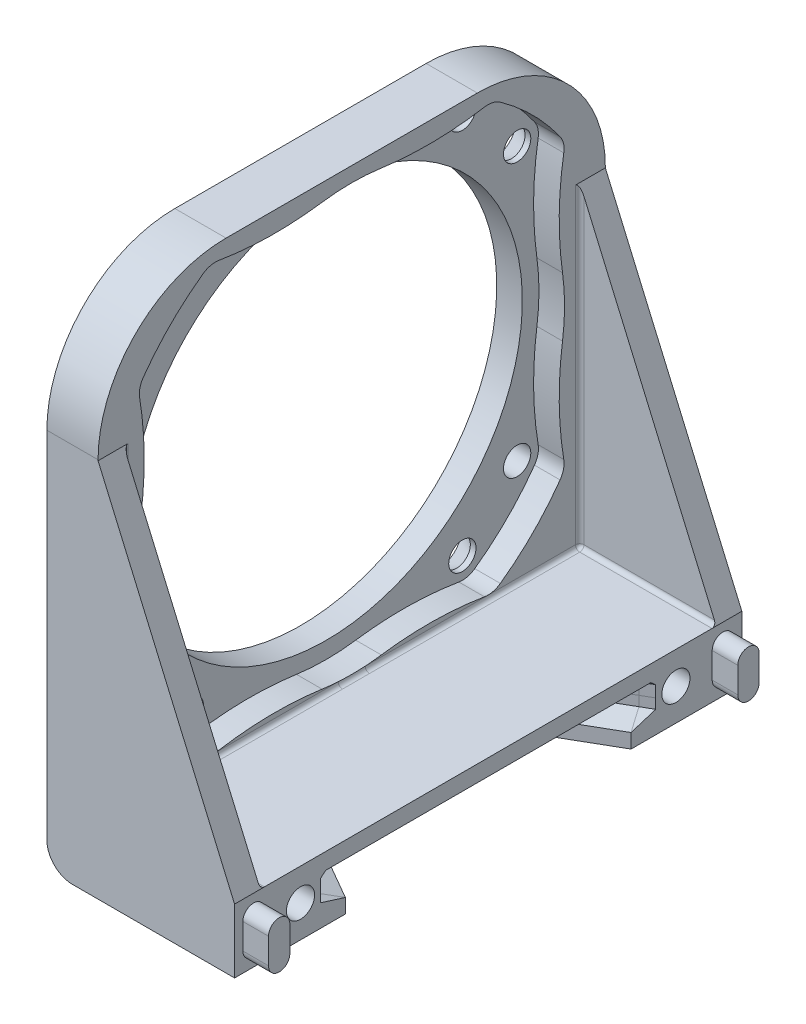
SolidWorks part; units mm, degrees
material "6061 合金"
ref_plane "前视基准面" through (0, 0, 0) normal (0, 0, 1) x (1, 0, 0)
ref_plane "上视基准面" through (0, 0, 0) normal (0, 1, 0) x (1, 0, 0)
ref_plane "右视基准面" through (0, 0, 0) normal (1, 0, 0) x (0, 0, -1)
other "Configuration Table"
sketch "草图1" plane through (0, 0, 0) normal (0, 1, 0) x (1, 0, 0)
  line L0 (0, 16.7432) -> (0, 29.7252)
  line L1 (0, 16.7432) -> (-14.5, 8.3716)
  line L2 (-14.5, 8.3716) -> (-14.5, -8.3716)
  line L3 (-14.5, -8.3716) -> (0, -16.7432)
  line L4 (0, -16.7432) -> (14.5, -8.3716) construction
  line L5 (14.5, -8.3716) -> (14.5, 8.3716) construction
  line L6 (14.5, 8.3716) -> (0, 16.7432) construction
  line L7 (0, 29.7252) -> (-22, 29.7252)
  line L8 (-22, 29.7252) -> (-22, -29.7252)
  line L9 (-22, -29.7252) -> (0, -29.7252)
  line L10 (0, -29.7252) -> (0, -16.7432)
  line L11 (-22, 0) -> (14.5, 0) construction
  circle A0 centre (0, 0) radius 14.5 construction
  dimension "D1" = 29
  dimension "D2" = 59.4504
  dimension "D3" = 22
extrude "凸台-拉伸1" add sketch "草图1" along normal blind 7.5
ref_plane "基准面3" through (12.8714, 0, 7.4313) normal (0.866, 0, 0.5) x (0, -1, 0)
sketch "草图2" plane through (-16.7286, 0, 58.7) normal (-0.866, 0, -0.5) x (-0.5, 0, 0.866)
  line L0 (-33.4573, 3.75) -> (-84.9428, 3.75) construction
  line L1 (-33.4573, 7.5) -> (-33.4573, 0) construction
  line L2 (-84.9428, 7.5) -> (-84.9428, 0) construction
  line L4 (-42.2, 3.75) -> (-42.2, 5.5919)
  line L8 (-44.7, 1.682) -> (-44.7, 3.75)
  line L10 (-42.2, 3.75) -> (-42.2, 2.5919)
  line L11 (-44.7, 1.682) -> (-42.2, 2.5919)
  line L12 (-44.7, 7.5) -> (-44.7, 0) construction
  line L13 (-42.2, 5.5919) -> (-44.7, 5.5919)
  line L14 (-44.7, 5.5919) -> (-44.7, 3.75)
  point P11 (-40.2, 3.75)
  point P12 (-43.7746, 3.75)
  dimension "D1" = 1.1581
  dimension "D2" = 2.5
  dimension "D3" = 20
  dimension "D4" = 3
ref_plane "基准面1" through (0, 3.75, 0) normal (0, 1, 0) x (1, 0, 0)
sketch "草图3" plane through (0, 3.75, 0) normal (0, 1, 0) x (1, 0, 0)
  line L0 (0, -16.7432) -> (-14.5, -8.3716) construction
  line L1 (-14.5, 8.3716) -> (0, 16.7432) construction
  line L2 (-14.5, -8.3716) -> (-14.5, 8.3716) construction
  line L3 (0, -16.7432) -> (-14.5, -8.3716)
  line L4 (-14.5, 8.3716) -> (0, 16.7432)
  line L5 (-14.5, -8.3716) -> (-14.5, 8.3716)
  line L6 (0, 16.7432) -> (15.4317, 25.6527)
  line L7 (0, -16.7432) -> (15.5318, -25.7104)
sweep "切除-扫描1" cut profiles "草图2" path "草图3"
fillet "圆角1" radius 5 4 edges at (-17, 3.171, -9.815) (-17, 3.171, 9.815) (-17, 4.671, -9.815) (-17, 4.671, 9.815)
fillet "圆角2" radius 1 4 edges at (-14.5, 0.841, -8.3716) (-14.5, 6.546, -8.3716) (-14.5, 0.841, 8.3716) (-14.5, 6.546, 8.3716)
sketch "草图4" plane through (0, 7.5, 0) normal (0, 1, 0) x (1, 0, 0)
  line L0 (-22, -29.7252) -> (0, -29.7252) construction
  line L1 (-22, 29.7252) -> (-19, 29.7252)
  line L2 (-22, 29.7252) -> (-22, -29.7252)
  line L3 (-22, -29.7252) -> (-19, -29.7252)
  line L4 (-19, 29.7252) -> (-19, -29.7252)
  dimension "D1" = 3
extrude "凸台-拉伸2" add sketch "草图4" along normal blind 55.6
sketch "草图5" plane through (-22, 0, 0) normal (-1, 0, 0) x (0, 0, 1)
  line L0 (-29.7252, 0) -> (29.7252, 0) construction
  line L1 (-27.5, 32.9) -> (0, 32.9) construction
  line L2 (-22.3882, 48.8693) -> (0, 32.9) construction
  line L3 (-15.9693, 55.2882) -> (0, 32.9) construction
  circle A0 centre (0, 32.9) radius 27.5 construction
  circle A1 centre (-22.3882, 48.8693) radius 1.6
  circle A2 centre (-15.9693, 55.2882) radius 1.6
  circle A3 centre (15.9693, 55.2882) radius 1.6
  circle A4 centre (22.3882, 48.8693) radius 1.6
  circle A5 centre (22.3882, 16.9307) radius 1.6
  circle A6 centre (15.9693, 10.5118) radius 1.6
  circle A7 centre (-15.9693, 10.5118) radius 1.6
  circle A8 centre (-22.3882, 16.9307) radius 1.6
  circle A9 centre (0, 32.9) radius 23
  point P25 (0, 32.9)
  dimension "D2" = 55
  dimension "D5" = 3.2
  dimension "D6" = 3.2
  dimension "D8" = 46
  dimension "D1" = 32.9
  dimension "D3" = 35.5
  dimension "D4" = 19
  dimension "D7" = 4
extrude "切除-拉伸1" cut sketch "草图5" against normal blind 55.6
ref_axis "基准轴1" through (-19, 10.5118, -15.9693) along (-1, 0, 0)
ref_plane "基准面2" through (0, 0, -15.9693) normal (0, 0, 1) x (-1, 0, 0)
sketch "草图6" plane through (0, 0, -15.9693) normal (0, 0, 1) x (-1, 0, 0)
  line L0 (22, -10.5118) -> (22, -7.5118)
  line L1 (19, -10.5118) -> (22, -10.5118) construction
  line L2 (22, -7.5118) -> (19.5, -9.0118)
  line L3 (19.5, -9.0118) -> (19.5, -10.5118)
  line L5 (22, -63.1) -> (22, 0) construction
  line L6 (19.5, -10.5118) -> (22, -10.5118)
  dimension "D1" = 3
  dimension "D2" = 1.5
  dimension "D3" = 2.5
revolve "切除-旋转1" cut sketch "草图6" angle 360 about axis through (-19, 10.5118, -15.9693) along (-1, 0, 0)
pattern_circular "阵列(圆周)1" count 4 every 90 about axis through (33.6, 32.9, 0) along (-1, 0, 0) of "切除-旋转1"
sketch "草图7" plane through (-19, 0, 0) normal (1, 0, 0) x (0, 0, -1)
  line L16 (-29.7252, 7.5) -> (29.7252, 7.5)
  line L17 (29.7252, 7.5) -> (29.7252, 63.1)
  line L18 (29.7252, 63.1) -> (-29.7252, 63.1)
  line L19 (-29.7252, 63.1) -> (-29.7252, 7.5)
  line L20 (-29.7252, 7.5) -> (29.7252, 7.5)
  line L21 (29.7252, 7.5) -> (29.7252, 63.1)
  line L22 (29.7252, 63.1) -> (-29.7252, 63.1)
  line L23 (-29.7252, 63.1) -> (-29.7252, 7.5)
  arc A76 (-15.5614, 57.7547) -> (-3.4705, 57.6074) centre (-9.0345, 97.2186) ccw
  arc A77 (3.4705, 57.6074) -> (-3.4705, 57.6074) centre (0, 32.9) ccw
  arc A78 (3.4705, 57.6074) -> (15.5614, 57.7547) centre (9.0345, 97.2186) ccw
  arc A79 (17.4211, 57.3235) -> (15.5614, 57.7547) centre (15.9693, 55.2882) ccw
  arc A80 (24.4235, 50.3211) -> (17.4211, 57.3235) centre (0, 32.9) ccw
  arc A81 (24.8547, 48.4614) -> (24.4235, 50.3211) centre (22.3882, 48.8693) ccw
  arc A82 (24.8547, 48.4614) -> (24.7074, 36.3705) centre (64.3186, 41.9345) ccw
  arc A83 (24.7074, 29.4295) -> (24.7074, 36.3705) centre (0, 32.9) ccw
  arc A84 (24.7074, 29.4295) -> (24.8547, 17.3386) centre (64.3186, 23.8655) ccw
  arc A85 (24.4235, 15.4789) -> (24.8547, 17.3386) centre (22.3882, 16.9307) ccw
  arc A86 (17.4211, 8.4765) -> (24.4235, 15.4789) centre (0, 32.9) ccw
  arc A87 (15.5614, 8.0453) -> (17.4211, 8.4765) centre (15.9693, 10.5118) ccw
  arc A88 (15.5614, 8.0453) -> (3.4705, 8.1926) centre (9.0345, -31.4186) ccw
  arc A89 (-3.4705, 8.1926) -> (3.4705, 8.1926) centre (0, 32.9) ccw
  arc A90 (-3.4705, 8.1926) -> (-15.5614, 8.0453) centre (-9.0345, -31.4186) ccw
  arc A91 (-17.4211, 8.4765) -> (-15.5614, 8.0453) centre (-15.9693, 10.5118) ccw
  arc A92 (-24.4235, 15.4789) -> (-17.4211, 8.4765) centre (0, 32.9) ccw
  arc A93 (-24.8547, 17.3386) -> (-24.4235, 15.4789) centre (-22.3882, 16.9307) ccw
  arc A94 (-24.8547, 17.3386) -> (-24.7074, 29.4295) centre (-64.3186, 23.8655) ccw
  arc A95 (-24.7074, 36.3705) -> (-24.7074, 29.4295) centre (0, 32.9) ccw
  arc A96 (-24.7074, 36.3705) -> (-24.8547, 48.4614) centre (-64.3186, 41.9345) ccw
  arc A97 (-24.4235, 50.3211) -> (-24.8547, 48.4614) centre (-22.3882, 48.8693) ccw
  arc A98 (-17.4211, 57.3235) -> (-24.4235, 50.3211) centre (0, 32.9) ccw
  arc A99 (-15.5614, 57.7547) -> (-17.4211, 57.3235) centre (-15.9693, 55.2882) ccw
  arc A100 (-15.5614, 57.7547) -> (-3.4705, 57.6074) centre (-9.0345, 97.2186) ccw
  arc A101 (3.4705, 57.6074) -> (-3.4705, 57.6074) centre (0, 32.9) ccw
  arc A102 (3.4705, 57.6074) -> (15.5614, 57.7547) centre (9.0345, 97.2186) ccw
  arc A103 (17.4211, 57.3235) -> (15.5614, 57.7547) centre (15.9693, 55.2882) ccw
  arc A104 (24.4235, 50.3211) -> (17.4211, 57.3235) centre (0, 32.9) ccw
  arc A105 (24.8547, 48.4614) -> (24.4235, 50.3211) centre (22.3882, 48.8693) ccw
  arc A106 (24.8547, 48.4614) -> (24.7074, 36.3705) centre (64.3186, 41.9345) ccw
  arc A107 (24.7074, 29.4295) -> (24.7074, 36.3705) centre (0, 32.9) ccw
  arc A108 (24.7074, 29.4295) -> (24.8547, 17.3386) centre (64.3186, 23.8655) ccw
  arc A109 (24.4235, 15.4789) -> (24.8547, 17.3386) centre (22.3882, 16.9307) ccw
  arc A110 (17.4211, 8.4765) -> (24.4235, 15.4789) centre (0, 32.9) ccw
  arc A111 (15.5614, 8.0453) -> (17.4211, 8.4765) centre (15.9693, 10.5118) ccw
  arc A112 (15.5614, 8.0453) -> (3.4705, 8.1926) centre (9.0345, -31.4186) ccw
  arc A113 (-3.4705, 8.1926) -> (3.4705, 8.1926) centre (0, 32.9) ccw
  arc A114 (-3.4705, 8.1926) -> (-15.5614, 8.0453) centre (-9.0345, -31.4186) ccw
  arc A115 (-17.4211, 8.4765) -> (-15.5614, 8.0453) centre (-15.9693, 10.5118) ccw
  arc A116 (-24.4235, 15.4789) -> (-17.4211, 8.4765) centre (0, 32.9) ccw
  arc A117 (-24.8547, 17.3386) -> (-24.4235, 15.4789) centre (-22.3882, 16.9307) ccw
  arc A118 (-24.8547, 17.3386) -> (-24.7074, 29.4295) centre (-64.3186, 23.8655) ccw
  arc A119 (-24.7074, 36.3705) -> (-24.7074, 29.4295) centre (0, 32.9) ccw
  arc A120 (-24.7074, 36.3705) -> (-24.8547, 48.4614) centre (-64.3186, 41.9345) ccw
  arc A121 (-24.4235, 50.3211) -> (-24.8547, 48.4614) centre (-22.3882, 48.8693) ccw
  arc A122 (-17.4211, 57.3235) -> (-24.4235, 50.3211) centre (0, 32.9) ccw
  arc A123 (-15.5614, 57.7547) -> (-17.4211, 57.3235) centre (-15.9693, 55.2882) ccw
  dimension "D1" = 0
  dimension "D2" = 0
extrude "凸台-拉伸3" add sketch "草图7" along normal blind 3
sketch "草图8" plane through (0, 0, 0) normal (1, 0, 0) x (0, 0, -1)
  line L0 (-29.7252, 0) -> (-16.7432, 0) construction
  line L1 (-29.7252, 7.5) -> (-26.7252, 7.5)
  line L2 (-29.7252, 7.5) -> (-29.7252, 0)
  line L3 (-29.7252, 0) -> (-26.7252, 0)
  line L4 (-26.7252, 7.5) -> (-26.7252, 0)
  line L5 (16.7432, 0) -> (29.7252, 0) construction
  line L6 (29.7252, 7.5) -> (26.7252, 7.5)
  line L7 (29.7252, 7.5) -> (29.7252, 0)
  line L8 (29.7252, 0) -> (26.7252, 0)
  line L9 (26.7252, 7.5) -> (26.7252, 0)
  dimension "D1" = 3
  dimension "D2" = 3
extrude "凸台-拉伸4" add sketch "草图8" along normal blind 15
sketch "草图9" plane through (0, 0, 29.7252) normal (0, 0, 1) x (1, 0, 0)
  line L0 (-16, 51.1) -> (13, 7.5)
  line L1 (13, 7.5) -> (-16, 7.5)
  line L2 (-16, 7.5) -> (-16, 51.1)
  line L4 (-22, 63.1) -> (-16, 63.1) construction
  line L5 (-16, 7.5) -> (15, 7.5) construction
  line L7 (15, 7.5) -> (15, 0) construction
  point P2 (0, 0)
  dimension "D1" = 12
  dimension "D2" = 2
extrude "凸台-拉伸5" add sketch "草图9" against normal blind 3
sketch "草图10" plane through (0, 0, -29.7252) normal (0, 0, -1) x (-1, 0, 0)
  line L3 (16, 7.5) -> (16, 51.1)
  line L4 (16, 51.1) -> (-13, 7.5)
  line L5 (-13, 7.5) -> (-15, 7.5)
  line L7 (16, 51.1) -> (-13, 7.5)
  line L8 (-13, 7.5) -> (-15, 7.5)
  line L13 (0, 0) -> (0, 7.5)
  line L14 (0, 0) -> (0, 7.5)
  line L15 (0, 7.5) -> (16, 7.5)
  line L16 (0, 7.5) -> (16, 7.5)
  line L17 (-15, 7.5) -> (-15, 0)
  line L18 (-15, 7.5) -> (-15, 0)
  line L19 (-15, 0) -> (0, 0)
  line L20 (-15, 0) -> (0, 0)
  line L23 (16, 7.5) -> (16, 51.1)
  dimension "D1" = 0
extrude "凸台-拉伸6" add sketch "草图10" against normal blind 3
sketch "草图12" plane through (0, 0, 0) normal (1, 0, 0) x (0, 0, -1)
  line L0 (20.35, 3.75) -> (-20.35, 3.75) construction
  line L1 (0, 0) -> (0, 6) construction
  point P0 (-22, 3.75)
  point P4 (22, 3.75)
  dimension "D1" = 44
hole_wizard "M4 螺纹孔1" positions "草图12" profile "草图13" tap size "M4" standard "GB"
sketch "草图13" plane through (0, 3.75, 22) normal (0, 1, 0) x (0, 0, -1)
  line L0 (0, 0) -> (0, 6.4914)
  line L1 (0, 6.4914) -> (1.65, 5.5)
  line L2 (1.65, 5.5) -> (1.65, 0)
  line L5 (1.65, 0) -> (0, 0)
  line L10 (0, 6.4914) -> (-1.65, 5.5) construction
  line L11 (0, -6.35) -> (0, 107.95) construction
  dimension "螺纹孔钻头直径" = 3.3
  dimension "螺纹孔钻头深度" = 5.5
  dimension "导头角度" = 118
cosmetic thread "孔螺蚊线1" parameters "D1"=4, "D2"=4
cosmetic thread "孔螺蚊线2" parameters "D1"=4, "D2"=4
sketch "草图14" plane through (15, 0, 0) normal (1, 0, 0) x (0, 0, -1)
  line L0 (-28.2252, 7.5) -> (-28.2252, 0) construction
  line L1 (-26.7252, 7.5) -> (-29.7252, 7.5) construction
  line L2 (-29.7252, 0) -> (-26.7252, 0) construction
  line L3 (-29.7252, 3.75) -> (29.7252, 3.75) construction
  line L4 (-29.7252, 7.5) -> (-29.7252, 0) construction
  line L5 (29.7252, 0) -> (29.7252, 7.5) construction
  line L6 (0, 0) -> (0, 6) construction
  line L8 (-28.2252, 5.75) -> (-28.2252, 1.75) construction
  line L9 (-27.4752, 5.75) -> (-27.4752, 1.75)
  line L10 (-28.9752, 5.75) -> (-28.9752, 1.75)
  line L11 (28.2252, 5.75) -> (28.2252, 1.75) construction
  line L12 (27.4752, 5.75) -> (27.4752, 1.75)
  line L13 (28.9752, 5.75) -> (28.9752, 1.75)
  arc A2 (-27.4752, 5.75) -> (-28.9752, 5.75) centre (-28.2252, 5.75) ccw
  arc A3 (-28.9752, 1.75) -> (-27.4752, 1.75) centre (-28.2252, 1.75) ccw
  arc A4 (27.4752, 5.75) -> (28.9752, 5.75) centre (28.2252, 5.75) cw
  arc A5 (28.9752, 1.75) -> (27.4752, 1.75) centre (28.2252, 1.75) cw
  point P19 (-28.2252, 3.75)
  point P27 (28.2252, 3.75)
  dimension "D1" = 1.5
  dimension "D2" = 4
extrude "切除-拉伸2" cut sketch "草图14" against normal blind 5.2
sketch "草图17" plane through (0, 0, 0) normal (0, -1, 0) x (1, 0, 0)
  line L0 (0, 26.7252) -> (0, 16.7432) construction
  line L1 (0, 16.7432) -> (-14, 8.6603) construction
  line L2 (-14.5, 7.7942) -> (-14.5, -7.7942) construction
  line L3 (0, -16.7432) -> (0, -26.7252) construction
  line L4 (-14, -8.6603) -> (0, -16.7432) construction
  line L5 (0, -16.7432) -> (0, -26.7252)
  line L6 (-14, -8.6603) -> (0, -16.7432)
  line L7 (-14.5, 7.7942) -> (-14.5, -7.7942)
  line L8 (0, 16.7432) -> (-14, 8.6603)
  line L9 (0, 26.7252) -> (0, 16.7432)
  circle A0 centre (0, 0) radius 22.95
  arc A1 (-14.5, -7.7942) -> (-14, -8.6603) centre (-13.5, -7.7942) ccw construction
  arc A2 (-14, 8.6603) -> (-14.5, 7.7942) centre (-13.5, 7.7942) ccw construction
  arc A3 (-14.5, -7.7942) -> (-14, -8.6603) centre (-13.5, -7.7942) ccw
  arc A4 (-14, 8.6603) -> (-14.5, 7.7942) centre (-13.5, 7.7942) ccw
  dimension "D1" = 45.9
sketch "草图28" plane through (-22, 0, 0) normal (-1, 0, 0) x (0, 0, 1)
  line L0 (29.7252, 63.1) -> (29.7252, 0) construction
  line L1 (-29.7252, 63.1) -> (29.7252, 63.1)
  line L2 (-29.7252, 63.1) -> (-29.7252, 59.6)
  line L3 (-29.7252, 59.6) -> (29.7252, 59.6)
  line L4 (29.7252, 63.1) -> (29.7252, 59.6)
  dimension "D1" = 3.5
extrude "切除-拉伸7" cut sketch "草图28" against normal blind 10
fillet "圆角5" radius 15 2 edges at (-19, 59.6, -29.7252) (-19, 59.6, 29.7252)
chamfer "倒角2" distance 0.5 angle 45 4 edges at (15, 3.75, -29.7252) (15, 3.75, -26.7252) (15, 3.75, 26.7252) (15, 3.75, 29.7252)
sketch "草图21" plane through (0, 0, 26.7252) normal (0, 0, -1) x (-1, 0, 0)
  line L0 (-14.5, 0) -> (-15, 0)
  line L1 (-15, 0) -> (-15, 7.5)
  line L2 (-15, 7.5) -> (-14.5, 7.5)
  line L7 (-13, 7.5) -> (-14.5, 7.5)
  line L8 (-14.5, 7.5) -> (-14.5, 0)
  line L9 (-14.5, 0) -> (0, 0)
  line L10 (0, 0) -> (0, 7.5)
  line L11 (0, 7.5) -> (16, 7.5)
  line L12 (0, 7.5) -> (16, 7.5)
  line L13 (16, 51.1) -> (-13, 7.5)
  line L14 (-13, 7.5) -> (-14.5, 7.5)
  line L16 (-14.5, 0) -> (0, 0)
  line L20 (16, 51.1) -> (-13, 7.5)
  line L24 (0, 0) -> (0, 7.5)
  line L25 (16, 7.5) -> (16, 51.1)
  line L28 (16, 7.5) -> (16, 51.1)
  dimension "D1" = 0
extrude "切除-拉伸5" cut sketch "草图21" against normal through all and the other way through all
sketch "草图22" plane through (0, 0, 29.7252) normal (0, 0, 1) x (1, 0, 0)
  line L0 (0, 7.5) -> (-16, 44.5)
  line L2 (-16, 44.5) -> (-16, 7.5)
  line L3 (-16, 7.5) -> (0, 7.5)
  dimension "D1" = 37
extrude "凸台-拉伸8" add sketch "草图22" against normal blind 3
sketch "草图23" plane through (0, 0, -29.7252) normal (0, 0, -1) x (-1, 0, 0)
  line L3 (0, 7.5) -> (16, 7.5)
  line L4 (16, 7.5) -> (16, 44.5)
  line L5 (16, 44.5) -> (0, 7.5)
  line L6 (0, 7.5) -> (16, 7.5)
  line L8 (16, 44.5) -> (0, 7.5)
  line L11 (16, 7.5) -> (16, 44.5)
  dimension "D1" = 0
extrude "凸台-拉伸9" add sketch "草图23" against normal blind 3
sketch "草图24" plane through (0, 0, 0) normal (1, 0, 0) x (0, 0, -1)
  line L0 (-29.7252, 3.75) -> (29.7252, 3.75) construction
  line L1 (-29.7252, 0) -> (-29.7252, 7.5) construction
  line L2 (29.7252, 0) -> (29.7252, 7.5) construction
  line L3 (0, 0) -> (0, 7.95) construction
  line L4 (-27.5, 5.25) -> (-27.5, 2.25) construction
  line L5 (-26.25, 5.25) -> (-26.25, 2.25)
  line L6 (-28.75, 5.25) -> (-28.75, 2.25)
  line L7 (27.5, 5.25) -> (27.5, 2.25) construction
  line L8 (26.25, 5.25) -> (26.25, 2.25)
  line L9 (28.75, 5.25) -> (28.75, 2.25)
  arc A3 (-26.25, 5.25) -> (-28.75, 5.25) centre (-27.5, 5.25) ccw
  arc A4 (-28.75, 2.25) -> (-26.25, 2.25) centre (-27.5, 2.25) ccw
  arc A5 (26.25, 5.25) -> (28.75, 5.25) centre (27.5, 5.25) cw
  arc A6 (28.75, 2.25) -> (26.25, 2.25) centre (27.5, 2.25) cw
  point P14 (-27.5, 3.75)
  point P19 (0, 0)
  point P22 (27.5, 3.75)
  dimension "D1" = 27.5
  dimension "D2" = 3
  dimension "D3" = 2.5
extrude "切除-拉伸6" cut sketch "草图24" against normal blind 3.2
chamfer "倒角3" distance 0.5 angle 45 9 edges at (-0.625, 5.5919, 19.2691) (-7.875, 5.5919, 15.0833) (-15.5355, 5.5919, 10.4637) (-16.8296, 5.5919, 8.2223) (-17, 5.5919, 0) (-16.8296, 5.5919, -8.2223) (-0.625, 5.5919, -19.2691) (-15.5355, 5.5919, -10.4637) (-7.875, 5.5919, -15.0833)
sketch "草图25" plane through (0, 7.5, 0) normal (0, 1, 0) x (1, 0, 0)
  line L0 (-14, 8.6603) -> (0, 16.7432) construction
  line L1 (0, -16.7432) -> (-14, -8.6603) construction
  line L2 (-14, 8.6603) -> (0, 16.7432)
  line L3 (0, -16.7432) -> (-14, -8.6603)
  line L4 (0, 16.7432) -> (0, -16.7432)
  line L5 (-14.5, 7.7942) -> (-14.5, -7.7942)
  arc A0 (-14, 8.6603) -> (-14.5, 7.7942) centre (-13.5, 7.7942) ccw construction
  arc A1 (-14.5, -7.7942) -> (-14, -8.6603) centre (-13.5, -7.7942) ccw construction
  arc A2 (-14.5, -7.7942) -> (-14, -8.6603) centre (-13.5, -7.7942) ccw
  arc A3 (-14, 8.6603) -> (-14.5, 7.7942) centre (-13.5, 7.7942) ccw
extrude "凸台-拉伸10" add sketch "草图25" against normal up to surface (1.9081 mm away) up to face at (-9.9409, 5.5919, -12.0515)
fillet "圆角6" radius 3 1 edges at (-22, 0, 0)
fillet "圆角7" radius 0.5 5 edges at (-8, 7.5, -26.7252) (-8, 7.5, 26.7252) (-16, 7.5, 0) (-16, 26, -26.7252) (-16, 26, 26.7252)
sketch "草图27" plane through (-3.2, 0, 0) normal (1, 0, 0) x (0, 0, -1)
  line L0 (26.25, 5.25) -> (26.25, 2.25) construction
  line L1 (28.75, 2.25) -> (28.75, 5.25) construction
  line L2 (-28.75, 5.25) -> (-28.75, 2.25) construction
  line L3 (-26.25, 2.25) -> (-26.25, 5.25) construction
  line L4 (26.25, 5.25) -> (26.25, 2.25)
  line L5 (28.75, 2.25) -> (28.75, 5.25)
  line L6 (-28.75, 5.25) -> (-28.75, 2.25)
  line L7 (-26.25, 2.25) -> (-26.25, 5.25)
  arc A0 (28.75, 5.25) -> (26.25, 5.25) centre (27.5, 5.25) ccw construction
  arc A1 (26.25, 2.25) -> (28.75, 2.25) centre (27.5, 2.25) ccw construction
  arc A2 (-26.25, 5.25) -> (-28.75, 5.25) centre (-27.5, 5.25) ccw construction
  arc A3 (-28.75, 2.25) -> (-26.25, 2.25) centre (-27.5, 2.25) ccw construction
  arc A4 (28.75, 5.25) -> (26.25, 5.25) centre (27.5, 5.25) ccw
  arc A5 (26.25, 2.25) -> (28.75, 2.25) centre (27.5, 2.25) ccw
  arc A6 (-26.25, 5.25) -> (-28.75, 5.25) centre (-27.5, 5.25) ccw
  arc A7 (-28.75, 2.25) -> (-26.25, 2.25) centre (-27.5, 2.25) ccw
extrude "凸台-拉伸11" add sketch "草图27" along normal blind 6.2
